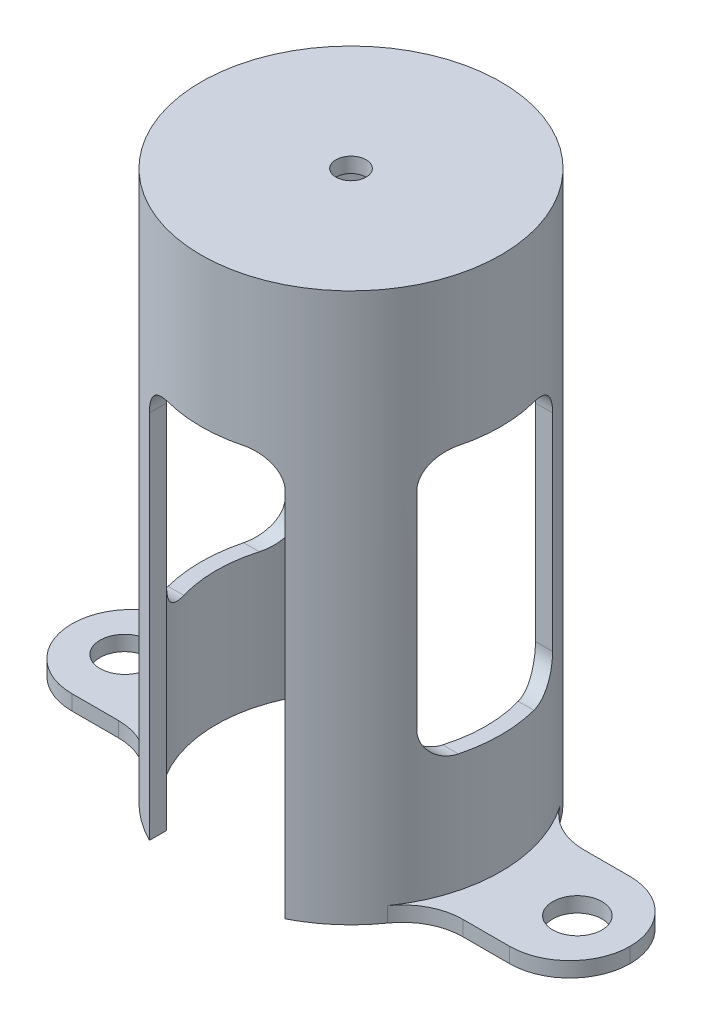
SolidWorks part; units mm, degrees
material "6061-T6 (SS)"
ref_plane "Front Plane" through (0, 0, 0) normal (0, 0, 1) x (1, 0, 0)
ref_plane "Top Plane" through (0, 0, 0) normal (0, 1, 0) x (1, 0, 0)
ref_plane "Right Plane" through (0, 0, 0) normal (1, 0, 0) x (0, 0, -1)
sketch "Sketch2" plane through (0, 0, 0) normal (0, 1, 0) x (1, 0, 0)
  circle A1 centre (0, 0) radius 9.9375
  dimension "D2" = 19.875
extrude "Boss-Extrude1" add sketch "Sketch2" along normal blind 35.384
sketch "Sketch4" plane through (0, 35.384, 0) normal (0, 1, 0) x (1, 0, 0)
  circle A0 centre (0, 0) radius 1
  dimension "D1" = 2
extrude "Cut-Extrude2" cut sketch "Sketch4" against normal through all
sketch "Sketch11" plane through (0, 0, 0) normal (0, -1, 0) x (1, 0, 0)
  line L0 (9.0969, 4) -> (18.5, 4)
  line L1 (-18.5, 4) -> (-9.0969, 4)
  line L2 (-18.5, 4) -> (-18.5, -4)
  line L3 (-18.5, -4) -> (-9.0969, -4)
  line L4 (18.5, 4) -> (18.5, -4)
  line L5 (-18.5, 4) -> (18.5, -4) construction
  line L6 (-18.5, -4) -> (18.5, 4) construction
  line L7 (9.0969, -4) -> (18.5, -4)
  arc A0 (9.0969, 4) -> (-9.0969, 4) centre (0, 0) ccw
  circle A1 centre (0, 0) radius 8.9375
  arc A2 (-9.0969, -4) -> (9.0969, -4) centre (0, 0) ccw
  point P0 (0, 0)
  dimension "D3" = 19.875
  dimension "D4" = 17.875
  dimension "D1" = 8
  dimension "D2" = 37
extrude "Boss-Extrude2" add sketch "Sketch11" along normal blind 1
sketch "Sketch12" plane through (0, 0, 0) normal (0, -1, 0) x (1, 0, 0)
  circle A0 centre (0, 0) radius 8.9375
  dimension "D1" = 17.875
extrude "Cut-Extrude7" cut sketch "Sketch12" against normal blind 34.384
ref_plane "Plane4" through (0, 0, 30) normal (0, 0, 1) x (1, 0, 0)
sketch "Sketch13" plane through (0, 0, 30) normal (0, 0, 1) x (1, 0, 0)
  line L0 (0, -10.9313) -> (0, 10.9313) construction
  line L1 (-4.5, 25.538) -> (4.5, 25.538)
  line L2 (-4.5, 25.538) -> (-4.5, -1)
  line L3 (-4.5, -1) -> (4.5, -1)
  line L4 (4.5, 25.538) -> (4.5, -1)
  line L5 (-4.5, 25.538) -> (4.5, -1) construction
  line L6 (-4.5, -1) -> (4.5, 25.538) construction
  line L7 (-9.0969, -1) -> (9.0969, -1) construction
  point P0 (0, 12.269)
  dimension "D1" = 26.538
  dimension "D2" = 9
extrude "Cut-Extrude8" cut sketch "Sketch13" against normal through all
ref_plane "Plane5" through (30, 0, 0) normal (1, 0, 0) x (0, 0, -1)
sketch "Sketch14" plane through (30, 0, 0) normal (1, 0, 0) x (0, 0, -1)
  line L0 (0, 10.9313) -> (0, -10.9313) construction
  line L1 (-4.5, 25.538) -> (4.5, 25.538)
  line L2 (-4.5, 25.538) -> (-4.5, 7.846)
  line L3 (-4.5, 7.846) -> (4.5, 7.846)
  line L4 (4.5, 25.538) -> (4.5, 7.846)
  line L5 (-4.5, 25.538) -> (4.5, 7.846) construction
  line L6 (-4.5, 7.846) -> (4.5, 25.538) construction
  line L7 (4, -1) -> (-4, -1) construction
  point P0 (0, 16.692)
  dimension "D2" = 9
  dimension "D1" = 17.692
  dimension "D3" = 17.692
extrude "Cut-Extrude9" cut sketch "Sketch14" against normal through all
fillet "Fillet3" radius 2 12 edges at (4.5, 25.538, -8.2911) (-4.5, 25.538, -8.2911) (-4.5, 25.538, 8.2911) (4.5, 25.538, 8.2911) (-8.2911, 25.538, 4.5) (-8.2911, 25.538, -4.5) (-8.2911, 7.846, -4.5) (-8.2911, 7.846, 4.5) (8.2911, 7.846, 4.5) (8.2911, 25.538, 4.5) (8.2911, 25.538, -4.5) (8.2911, 7.846, -4.5)
fillet "Fillet4" radius 4 8 edges at (9.0969, -0.5, -4) (18.5, -0.5, -4) (9.0969, -0.5, 4) (18.5, -0.5, 4) (-9.0969, -0.5, 4) (-18.5, -0.5, -4) (-9.0969, -0.5, -4) (-18.5, -0.5, 4)
sketch "Sketch15" plane through (0, 0, 0) normal (0, 1, 0) x (1, 0, 0)
  line L0 (-20.0112, 0) -> (20.0112, 0) construction
  circle A0 centre (-15, 0) radius 1.63
  circle A1 centre (15, 0) radius 1.63
  dimension "D3" = 3.26
  dimension "D4" = 3.26
  dimension "D1" = 15
  dimension "D2" = 15
extrude "Cut-Extrude10" cut sketch "Sketch15" against normal up to next
equation "\"FrangiboltTotalDiameter\"= 0.625in"
equation "\"FrangiboltTotalLength\"= 0.960in"
equation "\"FrangiboltThruHoleDiameter\"= 0.169in"
equation "\"EnclosureWallThickness\"= 1mm"
equation "\"EnclosureWallSpacing\"= 1mm"
equation "\"EnclosureInnerDiameter\"= \"FrangiboltTotalDiameter\" + 2 * \"EnclosureWallSpacing\""
equation "\"EnclosureOuterDiameter\"= \"FrangiboltTotalDiameter\" + 2 * \"EnclosureWallSpacing\" + 2 * \"EnclosureWallThickness\""
equation "\"EnclosureTotalLength\"= \"FrangiboltTotalLength\" + \"DamperLength\" + \"EnclosureWallThickness\""
equation "\"D2@Sketch2\"=\"EnclosureOuterDiameter\""
equation "\"D1@Boss-Extrude1\"=\"EnclosureTotalLength\""
equation "\"DamperLength\"= 10mm"
equation "\"EnclosureLip\"= 5mm"
equation "\"FrangiboltBoxWidth\"= 7mm"
equation "\"EnclosureMountingStandoff\"= 37mm"
equation "\"D2@Sketch11\"=\"EnclosureMountingStandoff\""
equation "\"D3@Sketch11\"=\"EnclosureOuterDiameter\""
equation "\"D4@Sketch11\"=\"EnclosureInnerDiameter\""
equation "\"D1@Boss-Extrude2\"=\"EnclosureWallThickness\""
equation "\"D1@Sketch12\"=\"EnclosureInnerDiameter\""
equation "\"D1@Cut-Extrude7\"=\"EnclosureTotalLength\"-\"EnclosureWallThickness\""
equation "\"D1@Sketch13\"=\"EnclosureTotalLength\"*0.75"
equation "\"D2@Sketch13\"=\"FrangiboltBoxWidth\"+2mm"
equation "\"D1@Sketch14\"=\"EnclosureTotalLength\"*0.5"
equation "\"D2@Sketch14\"=\"FrangiboltBoxWidth\"+2mm"
equation "\"D3@Sketch14\"=\"EnclosureTotalLength\"*0.5"
equation "\"EnclosureMountingHoleDiameter\" = 3.26mm"
equation "\"D3@Sketch15\"=\"EnclosureMountingHoleDiameter\""
equation "\"D4@Sketch15\"=\"EnclosureMountingHoleDiameter\""
